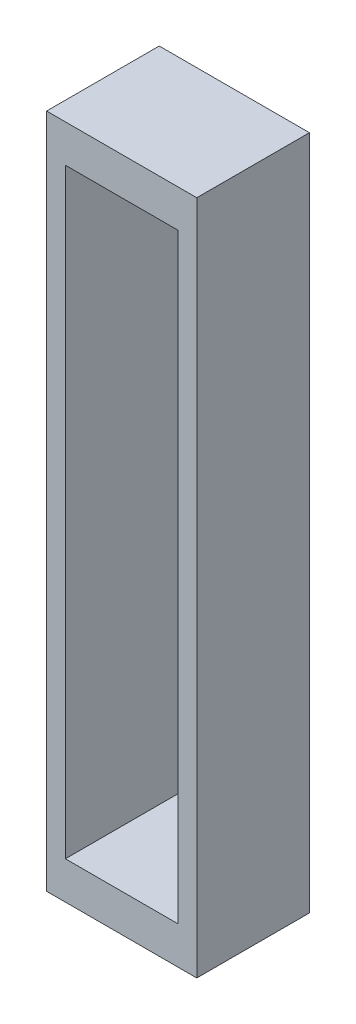
SolidWorks part; units mm, degrees
ref_plane "前视基准面" through (0, 0, 0) normal (0, 0, 1) x (1, 0, 0)
ref_plane "上视基准面" through (0, 0, 0) normal (0, 1, 0) x (1, 0, 0)
ref_plane "右视基准面" through (0, 0, 0) normal (1, 0, 0) x (0, 0, -1)
other "Configuration Table"
sketch "Sketch1" plane through (0, 0, 0) normal (0, 0, 1) x (1, 0, 0)
  line L1 (-20, 0) -> (20, 0)
  line L2 (-20, 0) -> (-20, 180)
  line L3 (-20, 180) -> (20, 180)
  line L4 (20, 0) -> (20, 180)
  line L5 (-20, 0) -> (20, 180) construction
  line L6 (-20, 180) -> (20, 0) construction
  point P0 (0, 90)
extrude "Boss-Extrude1" add sketch "Sketch1" along normal blind 30
sketch "Sketch2" plane through (0, 0, 0) normal (0, 0, 1) x (1, 0, 0)
  line L1 (-15, 10) -> (15, 10)
  line L2 (-15, 10) -> (-15, 170)
  line L3 (-15, 170) -> (15, 170)
  line L4 (15, 10) -> (15, 170)
  line L5 (-15, 10) -> (15, 170) construction
  line L6 (-15, 170) -> (15, 10) construction
  point P0 (0, 90)
extrude "Cut-Extrude1" cut sketch "Sketch2" along normal blind 30
sketch3d "3DSketch1"
  line L0 (0, 0, -100) -> (0, 0, 100) construction
ref_axis "Axis_Start" through (0, 0, -100) along (0, 0, 1)
sketch3d "3DSketch2"
  line L0 (0, 180, -100) -> (0, 180, 100) construction
ref_axis "Axis_End" through (0, 180, -100) along (0, 0, 1)
ref_plane "Mate_Mid" through (0, 0, 15) normal (0, 0, 1) x (1, 0, 0)
